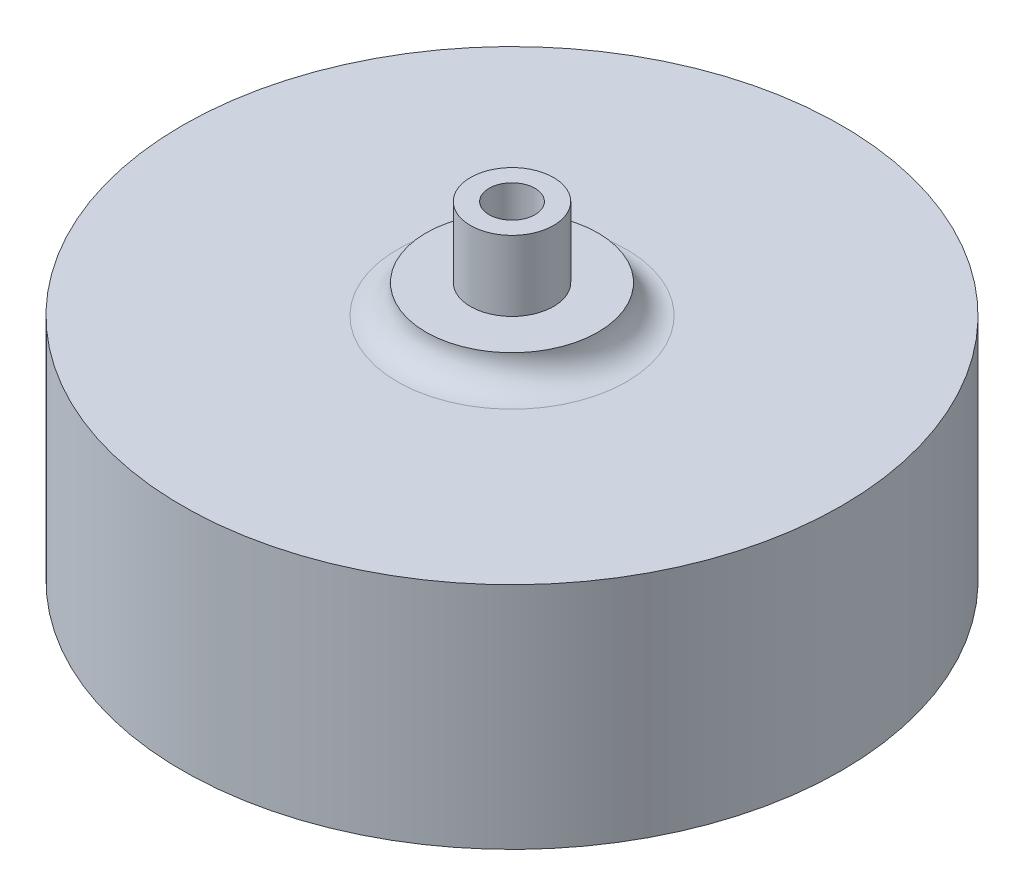
SolidWorks part; units mm, degrees
material "打印件"
ref_plane "前视基准面" through (0, 0, 0) normal (0, 0, 1) x (1, 0, 0)
ref_plane "上视基准面" through (0, 0, 0) normal (0, 1, 0) x (1, 0, 0)
ref_plane "右视基准面" through (0, 0, 0) normal (1, 0, 0) x (0, 0, -1)
sketch "草图1" plane through (0, 0, 0) normal (0, 0, 1) x (1, 0, 0)
  line L0 (0, 0) -> (1.3, 0)
  line L1 (1.3, 0) -> (1.3, -4.9)
  line L2 (1.3, -4.9) -> (4.4, -4.9)
  line L3 (4.4, -4.9) -> (4.4, -6.9)
  line L4 (4.4, -6.9) -> (21.4, -6.9)
  line L5 (21.4, -6.9) -> (21.4, -22.9)
  line L6 (21.4, -22.9) -> (4.4, -22.9)
  line L7 (4.4, -22.9) -> (4.4, -24.9)
  line L8 (4.4, -24.9) -> (1.3, -24.9)
  line L9 (1.3, -24.9) -> (1.3, -29.8)
  line L10 (1.3, -29.8) -> (0, -29.8)
  line L11 (-1.6, 5.74) -> (-1.6, -57.925) construction
  line L12 (0, 0) -> (0, -29.8)
  dimension "D1" = 4.9
  dimension "D2" = 1.3
  dimension "D3" = 6
  dimension "D4" = 2.9
  dimension "D5" = 2
  dimension "D6" = 23
  dimension "D7" = 16
  dimension "D8" = 2
  dimension "D9" = 6
  dimension "D10" = 2.9
  dimension "D11" = 1.3
  dimension "D12" = 4.9
revolve "旋转1" add sketch "草图1" angle 360 about L11
fillet "圆角1" radius 2 2 edges at (-7.6, -22.9, 0) (-7.6, -6.9, 0)
